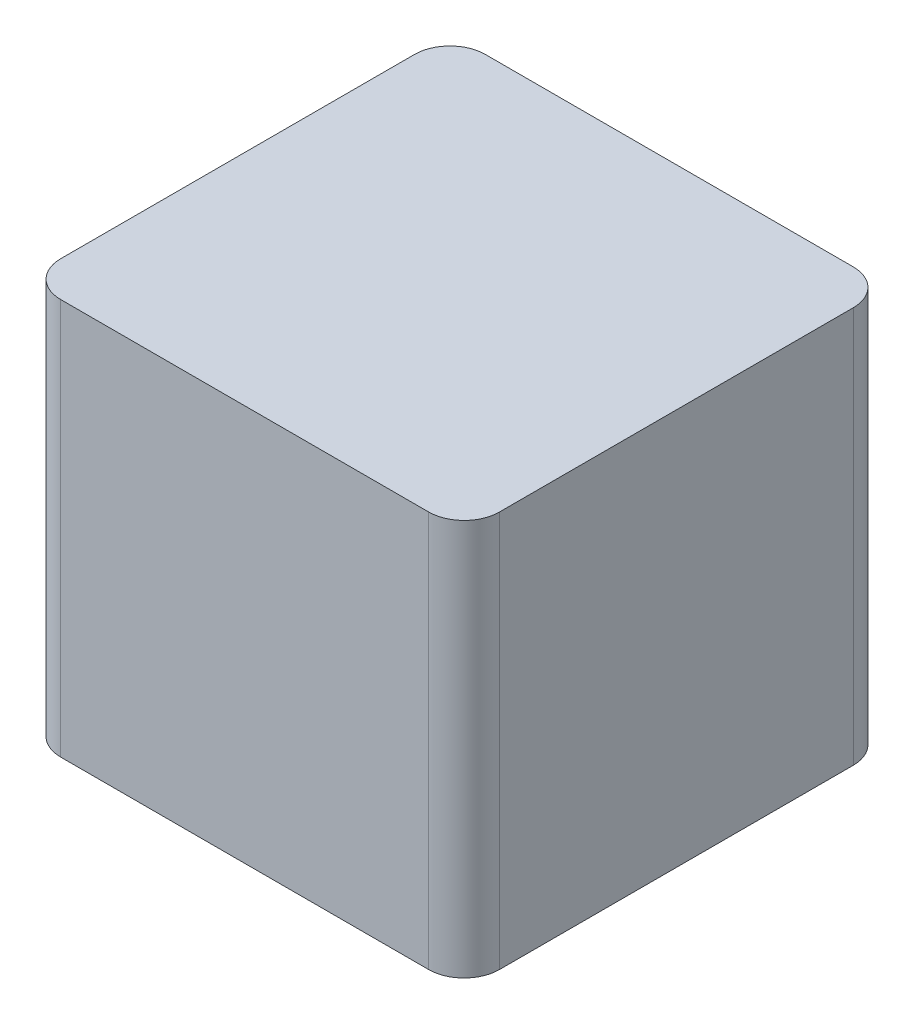
SolidWorks part; units mm, degrees
ref_plane "Front Plane" through (0, 0, 0) normal (0, 0, 1) x (1, 0, 0)
ref_plane "Top Plane" through (0, 0, 0) normal (0, 1, 0) x (1, 0, 0)
ref_plane "Right Plane" through (0, 0, 0) normal (1, 0, 0) x (0, 0, -1)
sketch "Sketch1" plane through (0, 0, 0) normal (0, 1, 0) x (1, 0, 0)
  line L1 (-52, -60) -> (52, -60)
  line L2 (-62, -50) -> (-62, 50)
  line L3 (-52, 60) -> (52, 60)
  line L4 (62, -50) -> (62, 50)
  line L5 (-62, -60) -> (62, 60) construction
  line L6 (-62, 60) -> (62, -60) construction
  arc A0 (-52, -60) -> (-62, -50) centre (-52, -50) cw
  arc A1 (52, -60) -> (62, -50) centre (52, -50) ccw
  arc A2 (52, 60) -> (62, 50) centre (52, 50) cw
  arc A3 (-62, 50) -> (-52, 60) centre (-52, 50) cw
  point P1 (0, 0)
  dimension "D3" = 10
  dimension "D1" = 124
  dimension "D2" = 120
extrude "Boss-Extrude1" add sketch "Sketch1" along normal blind 56 and the other way blind 56
